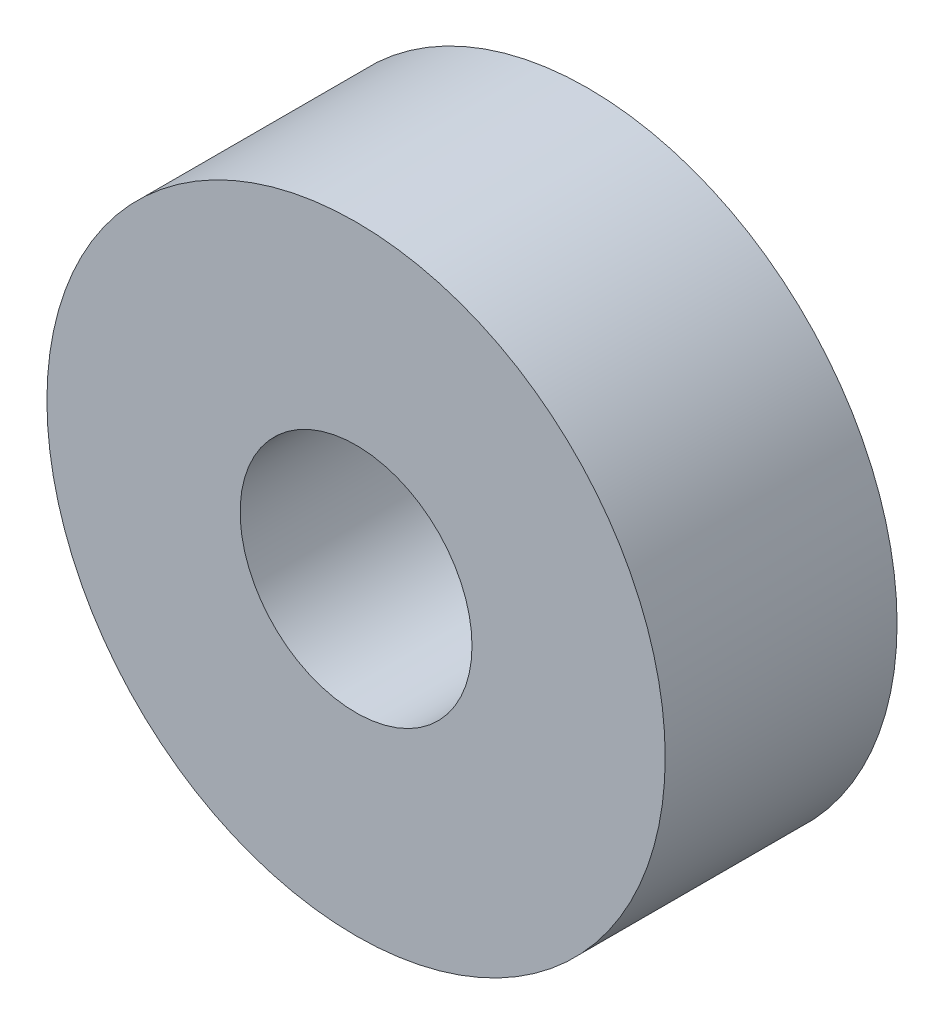
SolidWorks part; units mm, degrees
ref_plane "前视基准面" through (0, 0, 0) normal (0, 0, 1) x (1, 0, 0)
ref_plane "上视基准面" through (0, 0, 0) normal (0, 1, 0) x (1, 0, 0)
ref_plane "右视基准面" through (0, 0, 0) normal (1, 0, 0) x (0, 0, -1)
sketch "草图1" plane through (0, 0, 0) normal (0, 0, 1) x (1, 0, 0)
  circle A0 centre (0, 0) radius 4
  circle A1 centre (0, 0) radius 1.5
  dimension "D1" = 3
  dimension "D2" = 8
extrude "凸台-拉伸1" add sketch "草图1" along normal blind 1.5 and the other way blind 1.5
